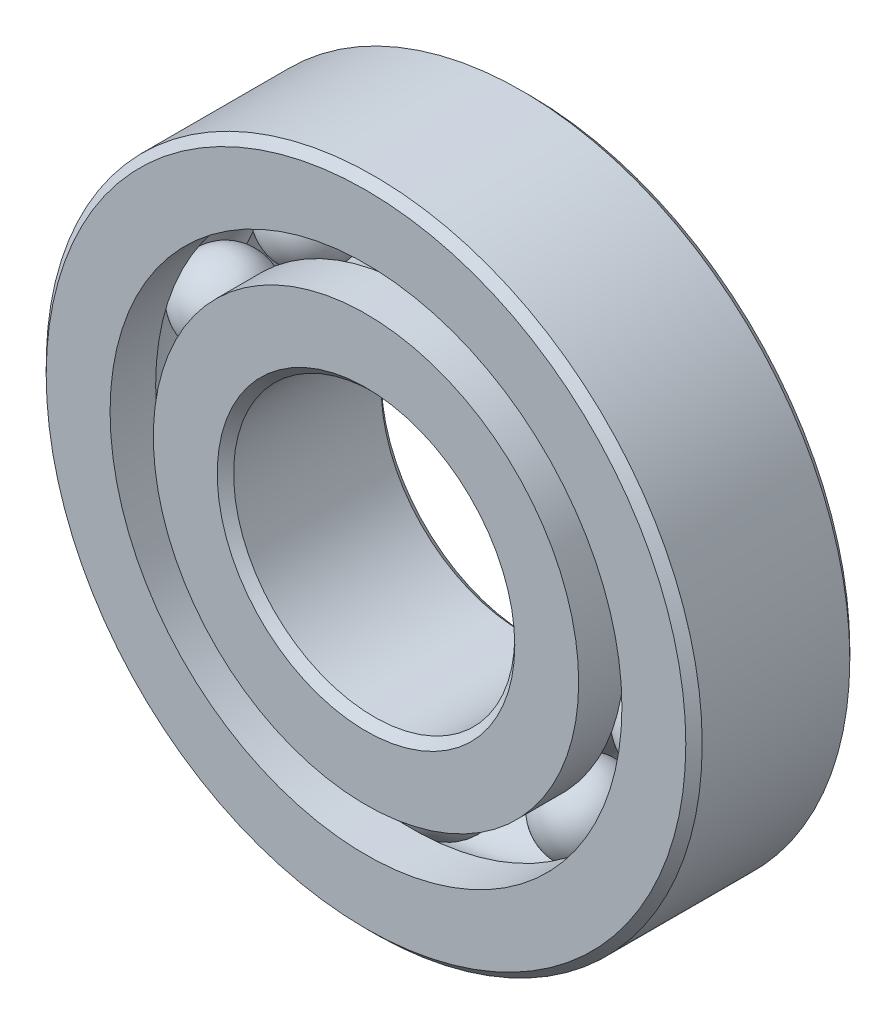
SolidWorks part; units mm, degrees
note: '?' marks a value the reader was unsure of.
material "Alloy Steel"
ref_plane "Front Plane" through (0, 0, 0) normal (0, 0, 1) x (1, 0, 0)
ref_plane "Top Plane" through (0, 0, 0) normal (0, 1, 0) x (1, 0, 0)
ref_plane "Right Plane" through (0, 0, 0) normal (1, 0, 0) x (0, 0, -1)
sketch "Sketch1" plane through (0, 0, 0) normal (1, 0, 0) x (0, 0, -1)
  line L0 (-2.7781, 0) -> (2.7781, 0) construction
  line L1 (0, 11.1125) -> (0, -11.1125) construction
  line L2 (2.5003, 11.1125) -> (-2.5003, 11.1125)
  line L3 (-2.5003, 11.1125) -> (-2.7781, 10.8347)
  line L4 (-2.7781, 10.8347) -> (-2.7781, 8.6702)
  line L5 (-2.7781, 8.6702) -> (-1.2347, 8.6702)
  line L6 (2.7781, 8.6702) -> (1.2347, 8.6702)
  line L7 (2.7781, 10.8347) -> (2.7781, 8.6702)
  line L8 (2.5003, 11.1125) -> (2.7781, 10.8347)
  line L9 (0, 11.1125) -> (0, 7.9375) construction
  line L10 (0, 7.9375) -> (0, 4.7625) construction
  arc A0 (-1.2347, 8.6702) -> (1.2347, 8.6702) centre (0, 7.9375) cw
  point P14 (0, 4.7625)
  dimension "Width" = 5.5562
  dimension "OD" = 22.225
  dimension "D1" = 45
  dimension "D2" = 0.2778
  dimension "Shaft Dia" = 9.525
  dimension "D3" = 2.4694
  dimension "D4" = 0.7327
revolve "Revolve1" add sketch "Sketch1" angle 360 about L0
sketch "Sketch3" plane through (0, 0, 0) normal (1, 0, 0) x (0, 0, -1)
  line L0 (-2.7781, 7.2048) -> (-1.2347, 7.2048)
  line L1 (0, 11.1125) -> (0, -11.1125) construction
  line L2 (-2.7781, 10.8347) -> (-2.7781, 8.6702) construction
  line L3 (-2.7781, 7.2048) -> (-2.7781, 5.0403)
  line L4 (-2.5003, 11.1125) -> (-2.7781, 10.8347) construction
  line L5 (-2.7781, 5.0403) -> (-2.5003, 4.7625)
  line L6 (-2.5003, 4.7625) -> (2.5003, 4.7625)
  line L7 (2.5003, 11.1125) -> (2.5003, -11.1125) construction
  line L8 (2.5003, 4.7625) -> (2.7781, 5.0403)
  line L9 (2.7781, -10.8347) -> (2.7781, 10.8347) construction
  line L10 (2.7781, 5.0403) -> (2.7781, 7.2048)
  line L11 (2.7781, 7.2048) -> (1.2347, 7.2048)
  line L13 (2.5003, 11.1125) -> (2.7781, 10.8347) construction
  arc A0 (1.2347, 8.6702) -> (-1.2347, 8.6702) centre (0, 7.9375) ccw construction
  arc A1 (1.2347, 7.2048) -> (-1.2347, 7.2048) centre (0, 7.9375) cw
revolve "Revolve3" add sketch "Sketch3" angle 360 about L0
sketch "Sketch4" plane through (0, 0, 0) normal (1, 0, 0) x (0, 0, -1)
  line L0 (-1.4357, 7.9375) -> (1.4357, 7.9375)
  arc A2 (-1.4357, 7.9375) -> (1.4357, 7.9375) centre (0, 7.9375) cw
  arc A3 (1.2347, 8.6702) -> (-1.2347, 8.6702) centre (0, 7.9375) ccw construction
revolve "Revolve4" add sketch "Sketch4" angle 360 about L0
ref_axis "Axis1" through (0, 0, -2.7781) along (0, 0, 1)?
pattern_circular "CirPattern1" count 10 every 36 about axis through (0, 0, 0) along (0, 0, 1) of bodies 104
sketch "Sketch5" plane through (0, 0, 0) normal (1, 0, 0) x (0, 0, -1)
  line L0 (-2.7781, 8.6702) -> (-1.2347, 8.6702) construction
  line L1 (-2.6392, 8.6702) -> (-1.4357, 8.6702)
  line L2 (-2.6392, 8.6702) -> (-2.6392, 7.2048)
  line L3 (-2.6392, 7.2048) -> (-1.4357, 7.2048)
  line L4 (-1.4357, 8.6702) -> (-1.4357, 7.2048)
  line L5 (-2.7781, 7.2048) -> (-1.2347, 7.2048) construction
  line L6 (2.7781, 8.6702) -> (1.2347, 8.6702) construction
  line L7 (2.6392, 8.6702) -> (1.4357, 8.6702)
  line L8 (2.6392, 8.6702) -> (2.6392, 7.2048)
  line L9 (2.6392, 7.2048) -> (1.4357, 7.2048)
  line L10 (1.4357, 8.6702) -> (1.4357, 7.2048)
  line L11 (2.7781, 7.2048) -> (1.2347, 7.2048) construction
  line L12 (-2.5003, 11.1125) -> (-2.7781, 10.8347) construction
  point P18 (-2.6392, 10.9736)
revolve "Revolve5" [suppressed] add sketch "Sketch5" angle 360 about L0
equation "\"D2@Sketch1\" = \"Width@Sketch1\"*.05"
equation "\"D3@Sketch1\" = \"Width@Sketch1\"/2.25"
equation "\"D4@Sketch1\" = (((\"OD@Sketch1\"-\"Width@Sketch1\")/2)/3.25)/3.5"
equation "\"D2@CirPattern1\" = 360/\"Balls@CirPattern1\""
